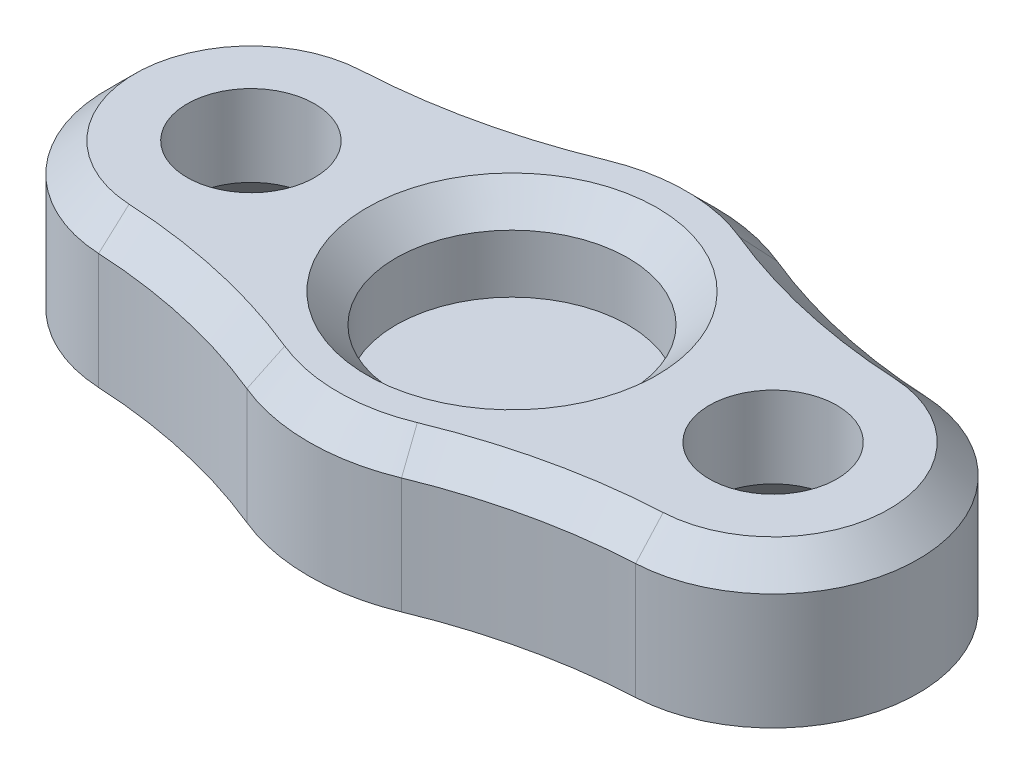
SolidWorks part; units mm, degrees
ref_plane "Front Plane" through (0, 0, 0) normal (0, 0, 1) x (1, 0, 0)
ref_plane "Top Plane" through (0, 0, 0) normal (0, 1, 0) x (1, 0, 0)
ref_plane "Right Plane" through (0, 0, 0) normal (1, 0, 0) x (0, 0, -1)
sketch "Sketch1" plane through (0, 0, 0) normal (0, 0, 1) x (1, 0, 0)
  line L0 (0, 0) -> (0, 7.0462) construction
  line L1 (0, 0) -> (-3.5, 0)
  line L2 (-3.5, 0) -> (-3.5, 2.5)
  line L3 (-3.5, 2.5) -> (-2, 2.5)
  line L4 (-2, 2.5) -> (-2, 1)
  line L5 (-2, 1) -> (0, 1)
  line L6 (0, 0) -> (0, 1)
  dimension "D1" = 2
  dimension "D2" = 1.5
  dimension "D3" = 1
  dimension "D4" = 1.5
revolve "Revolve1" add sketch "Sketch1" angle 360 about L0
chamfer "Chamfer2" distance 0.5 angle 45 1 edges at (0, 2.5, -2)
sketch "Sketch2" plane through (0, 2.5, 0) normal (0, 1, 0) x (1, 0, 0)
  line L0 (-2.4495, -2.5) -> (-8.5, -2.5)
  line L1 (-8.5, -2.5) -> (-8.5, 2.5)
  line L2 (-8.5, 2.5) -> (-2.4495, 2.5)
  line L3 (-8.5, 0) -> (-3.5, 0) construction
  circle A0 centre (0, 0) radius 3.5 construction
  arc A1 (-2.4495, 2.5) -> (-2.4495, -2.5) centre (0, 0) ccw
  point P2 (-8.5, 0)
  dimension "D1" = 5
extrude "Boss-Extrude1" add sketch "Sketch2" against normal up to surface (2.5 mm away) up to face at (0, 0, -3.5)
hole_wizard "CSK for M2 Flat Head Machine Screw1" positions "Sketch3" profile "Sketch4" countersink size "M2" standard "ANSI Metric"
sketch "Sketch3" plane through (0, 0, 0) normal (0, -1, 0) x (-1, 0, 0)
  point P0 (4.5, 0)
  dimension "D1" = 4.5
sketch "Sketch4" plane through (-4.5, 0, 0) normal (1, 0, 0) x (0, 0, -1)
  line L0 (0, 0) -> (0, 5.6609)
  line L1 (0, 5.6609) -> (1.1, 5)
  line L2 (1.1, 5) -> (1.1, 1.1)
  line L3 (1.1, 1.1) -> (2.2, 0)
  line L5 (2.2, 0) -> (0, 0)
  line L6 (-1.1, 1.1) -> (-2.2, 0) construction
  line L10 (0, 5.6609) -> (-1.1, 5) construction
  line L11 (0, -6.35) -> (0, 107.95) construction
  dimension "Hole Dia." = 2.2
  dimension "Hole Depth" = 5
  dimension "Near C'Sink Dia." = 4.4
  dimension "Near C'Sink Angle" = 90
  dimension "Drill Angle" = 118
sketch "Sketch5" plane through (0, 0, 0) normal (0, -1, 0) x (1, 0, 0)
  line L1 (-2.4495, 2.5) -> (-8.5, 2.5) construction
  line L2 (-2.4495, 2.5) -> (-8.5, 2.5) construction
  line L3 (-8.5, -2.5) -> (-2.4495, -2.5) construction
  line L4 (-4.5, -2.5) -> (-8.5, -2.5)
  line L5 (-8.5, -2.5) -> (-8.5, 2.5)
  line L9 (-8.5, 2.5) -> (-4.5, 2.5)
  arc A0 (-4.5, -2.5) -> (-4.5, 2.5) centre (-4.5, 0) cw
extrude "Cut-Extrude1" cut sketch "Sketch5" against normal through all both and the other way through all
pattern_circular "CirPattern1" count 2 over 360 about axis through (0, 0, 0) along (0, -1, 0) of "CSK for M2 Flat Head Machine Screw1", "Boss-Extrude1", "Cut-Extrude1" reverse direction yes
fillet "Fillet1" radius 10 4 edges at (-2.4495, 1.25, -2.5) (2.4495, 1.25, -2.5) (2.4495, 1.25, 2.5) (-2.4495, 1.25, 2.5)
chamfer "Chamfer3" distance 0.5 angle 45 8 edges at (-2.9486, 2.5, 2.7265) (0, 2.5, 3.5) (-7, 2.5, 0) (2.9486, 2.5, 2.7265) (-2.9486, 2.5, -2.7265) (7, 2.5, 0) (0, 2.5, -3.5) (2.9486, 2.5, -2.7265)
